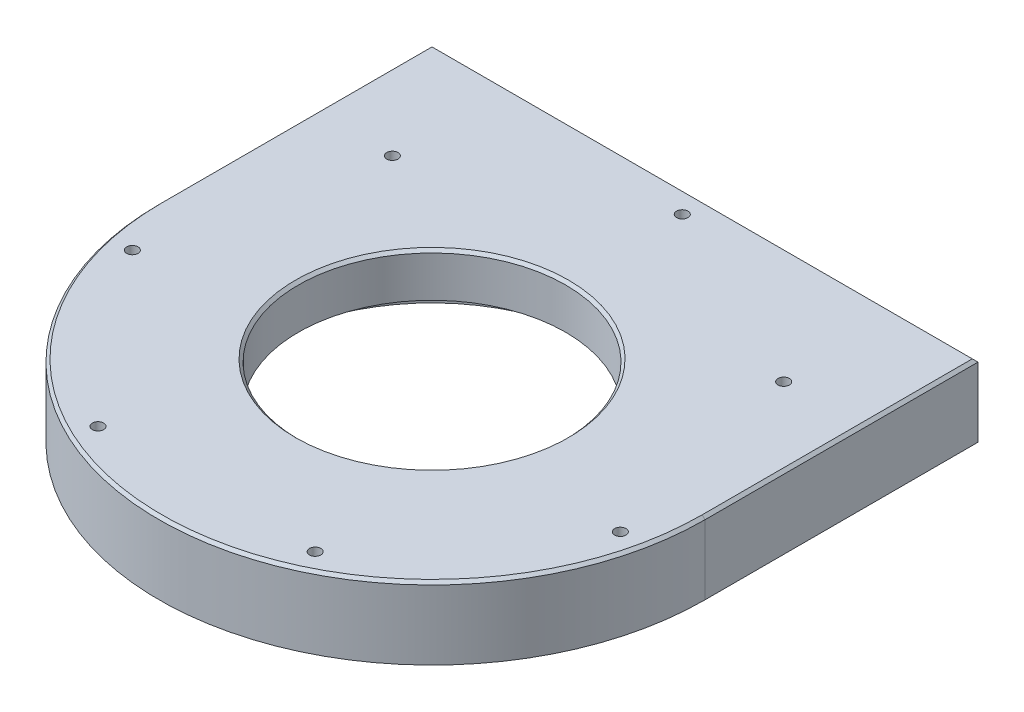
SolidWorks part; units mm, degrees
ref_plane "Front Plane" through (0, 0, 0) normal (0, 0, 1) x (1, 0, 0)
ref_plane "Top Plane" through (0, 0, 0) normal (0, 1, 0) x (1, 0, 0)
ref_plane "Right Plane" through (0, 0, 0) normal (1, 0, 0) x (0, 0, -1)
ref_axis "X Axis" through (-88.99, 0, 0) along (1, 0, 0)
ref_axis "Y Axiz" through (0, 0, 55) along (0, 0, -1)
ref_axis "Z Axis" through (0, 55, 0) along (0, -1, 0)
sketch "Sketch2" plane through (0, 0, 0) normal (0, 1, 0) x (1, 0, 0)
  line L0 (-48, 0) -> (-48, 48)
  line L1 (-52.8, 0) -> (52.8, 0) construction
  line L2 (-48, 48) -> (48, 48)
  line L3 (48, 48) -> (48, 0)
  line L4 (48, 0) -> (-48, 0)
  dimension "D1" = 48
sketch "Sketch1" plane through (0, 0, 0) normal (0, 1, 0) x (1, 0, 0)
  line L1 (34.4006, 27.4336) -> (18.373, 14.652) construction
  circle A0 centre (0, 0) radius 23.5
  circle A1 centre (0, 0) radius 48
  circle A2 centre (0, 0) radius 44 construction
  circle A3 centre (0, 44) radius 1
  circle A4 centre (34.4006, 27.4336) radius 1
  circle A5 centre (42.8968, -9.7909) radius 1
  circle A6 centre (19.0909, -39.6426) radius 1
  circle A7 centre (-19.0909, -39.6426) radius 1
  circle A8 centre (-42.8968, -9.7909) radius 1
  circle A9 centre (-34.4006, 27.4336) radius 1
  point P24 (0, 0)
  dimension "D1" = 47
  dimension "D2" = 96
  dimension "D3" = 88
  dimension "D4" = 2
  dimension "D5" = 7
extrude "Boss-Extrude1" add sketch "Sketch2" along normal blind 12.7
extrude "Boss-Extrude2" add sketch "Sketch1" along normal blind 12.7
extrude "Cut-Extrude1" cut sketch "Sketch1<2>" along normal blind 12.7 contours A4 | A3 | A9 | A0
sketch "Sketch1<2>" plane through (0, 0, 0) normal (0, 1, 0) x (1, 0, 0) same geometry as "Sketch1"
sketch "Sketch3" plane through (0, 0, 0) normal (0, 1, 0) x (1, 0, 0)
  circle A0 centre (0, 0) radius 30
  dimension "D1" = 60
extrude "Cut-Extrude3" cut sketch "Sketch3" along normal blind 5
chamfer "Chamfer1" distance 0.5 angle 45 5 edges at (0, 12.7, 23.5) (48, 12.7, -24) (0, 12.7, 48) (-48, 12.7, -24) (0, 12.7, -48)
